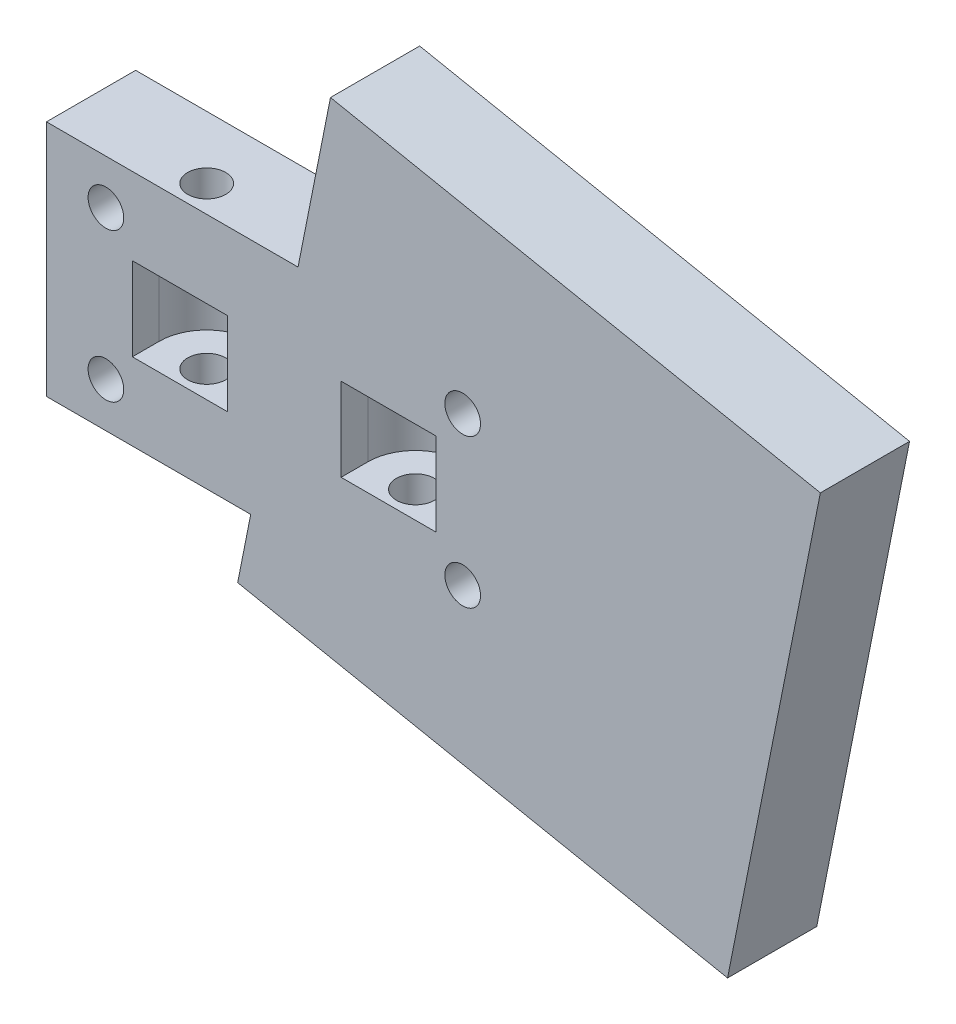
SolidWorks part; units mm, degrees
ref_plane "Front Plane" through (0, 0, 0) normal (0, 0, 1) x (1, 0, 0)
ref_plane "Top Plane" through (0, 0, 0) normal (0, 1, 0) x (1, 0, 0)
ref_plane "Right Plane" through (0, 0, 0) normal (1, 0, 0) x (0, 0, -1)
sketch "Sketch1" plane through (0, 0, 0) normal (0, 0, 1) x (1, 0, 0)
  line L2 (-38.1, -12.7) -> (-38.1, 12.7)
  line L3 (-38.1, 12.7) -> (38.1, 12.7)
  line L10 (38.1, -12.7) -> (38.1, 12.7)
  line L11 (-38.1, -12.7) -> (38.1, -12.7)
  line L14 (-38.1, 12.7) -> (38.1, -12.7) construction
  point P2 (0, 0)
  dimension "D1" = 76.2
  dimension "D2" = 25.4
extrude "Boss-Extrude1" add sketch "Sketch1" along normal blind 9.525
sketch "Sketch6" plane through (0, 0, 9.525) normal (0, 0, -1) x (-1, 0, 0)
  line L4 (17.6791, -19.7089) -> (-34.6359, -30.115)
  line L6 (17.6791, -19.7089) -> (7.7686, 30.115)
  line L23 (-34.6359, -30.115) -> (-44.5465, 19.7089)
  line L24 (7.7686, 30.115) -> (-44.5465, 19.7089)
  line L25 (17.6791, -19.7089) -> (-44.5465, 19.7089) construction
  line L26 (-34.6359, -30.115) -> (7.7686, 30.115) construction
  line L27 (-38.1, 12.7) -> (38.1, 12.7) construction
  point P0 (-14.1951, 0)
  point P1 (-13.4337, 0)
  dimension "D1" = 53.34
  dimension "D2" = 50.8
  dimension "D3" = 11.25
extrude "Boss-Extrude2" add sketch "Sketch6" along normal up to surface (9.525 mm away) up to face at (0, 0, 0)
sketch "Sketch4" plane through (0, 0, 0) normal (0, 1, 0) x (1, 0, 0)
  line L7 (-11.2326, -9.525) -> (-38.1, -9.525) construction
  line L8 (-28.9242, -6.6675) -> (-28.9242, -9.525)
  line L9 (-18.7643, -6.6675) -> (-18.7642, -9.525)
  line L10 (-18.7642, -9.525) -> (-28.9242, -9.525)
  line L11 (-38.1, -9.525) -> (-38.1, 0) construction
  arc A2 (-18.7643, -6.6675) -> (-28.9242, -6.6675) centre (-23.8442, -6.6675) ccw
  dimension "D1" = 10.16
  dimension "D2" = 2.8575
  dimension "D3" = 14.2558
extrude "Cut-Extrude2" cut sketch "Sketch4" against normal mid plane 8.89
ref_plane "Plane3" through (-12.7, 0, 0) normal (-1, 0, 0) x (0, 0, 1)
sketch "Sketch2" plane through (0, 0, 9.525) normal (0, 0, 1) x (1, 0, 0)
  line L0 (-38.1, -12.7) -> (-16.285, -12.7) construction
  line L1 (-38.1, 12.7) -> (-38.1, -12.7) construction
  circle A0 centre (-31.75, 7.9375) radius 1.905
  dimension "D1" = 3.81
  dimension "D2" = 20.6375
  dimension "D3" = 6.35
extrude "Cut-Extrude1" cut sketch "Sketch2" against normal up to surface (9.525 mm away) up to face at (-6.2479, 0, 0)
sketch "Sketch5" plane through (0, 12.7, 0) normal (0, 1, 0) x (1, 0, 0)
  line L0 (-11.2326, -9.525) -> (-38.1, -9.525) construction
  line L1 (-38.1, -9.525) -> (-38.1, 0) construction
  circle A0 centre (-23.8442, -6.6675) radius 2.032
  dimension "D3" = 4.064
  dimension "D1" = 2.8575
  dimension "D2" = 14.2558
extrude "Cut-Extrude3" cut sketch "Sketch5" along normal blind 3.175 and the other way through all
mirror "Mirror1" about plane through (0, 0, 0) normal (0, 1, 0) of "Cut-Extrude1"
mirror "Mirror2" about plane through (-12.7, 0, 0) normal (-1, 0, 0) of "Mirror1", "Cut-Extrude3", "Cut-Extrude2"
